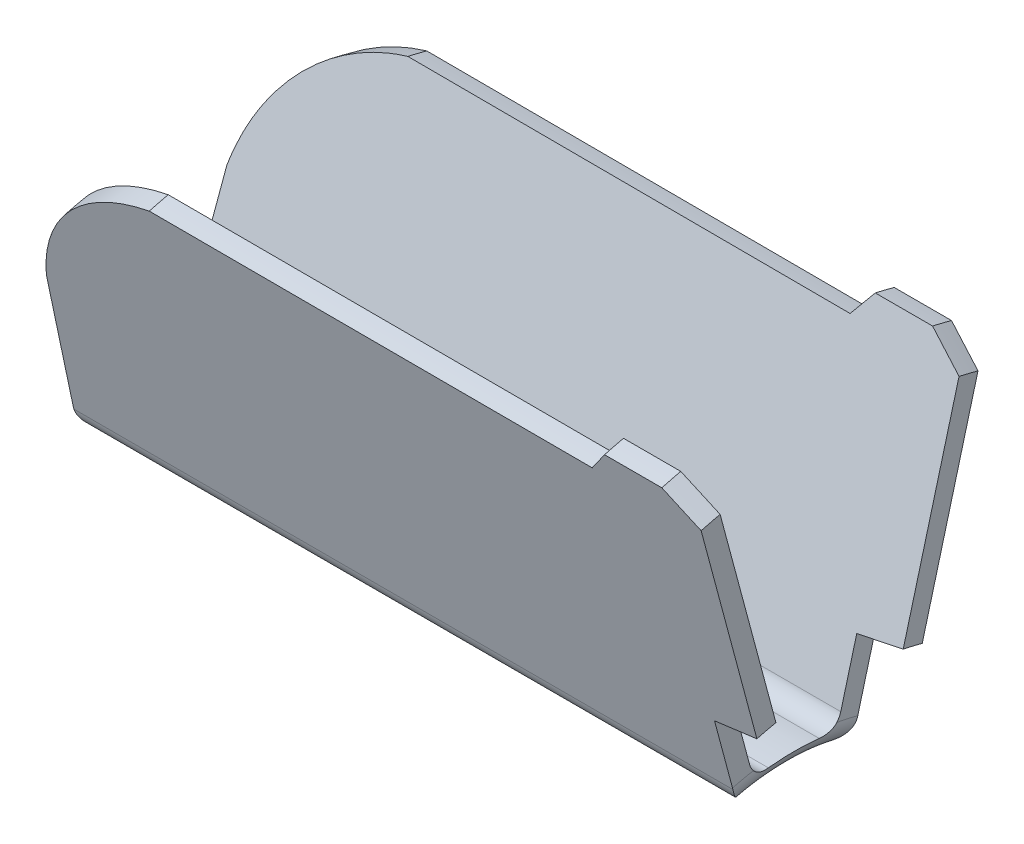
SolidWorks part; units mm, degrees
material "AISI 1045 Steel, cold drawn"
ref_plane "Front Plane" through (0, 0, 0) normal (0, 0, 1) x (1, 0, 0)
ref_plane "Top Plane" through (0, 0, 0) normal (0, 1, 0) x (1, 0, 0)
ref_plane "Right Plane" through (0, 0, 0) normal (1, 0, 0) x (0, 0, -1)
sketch "Sketch1" plane through (0, 0, 0) normal (0, 0, 1) x (1, 0, 0)
  line L0 (0, 0) -> (70.39, 0) construction
  line L1 (-21.1448, -22.76) -> (121.8609, -22.76) construction
  line L2 (70.39, 0) -> (75.12, 0) construction
  line L3 (70.39, 0) -> (70.39, 10.41)
  line L4 (70.39, 10.41) -> (75.12, 11.25)
  line L5 (75.12, 11.25) -> (75.12, 34.19)
  line L6 (75.12, 34.19) -> (71.6166, 36.83)
  line L7 (75.12, 34.19) -> (63.52, 34.19) construction
  line L8 (71.6166, 36.83) -> (65.5166, 36.83)
  line L9 (65.5166, 36.83) -> (63.52, 34.19)
  line L10 (16.39, 0) -> (16.39, 34.32) construction
  line L11 (63.52, 34.19) -> (16.39, 34.32)
  line L12 (0, 0) -> (1.2784, 18.282)
  line L13 (0, 0) -> (70.39, 0)
  arc A0 (1.2784, 18.282) -> (16.39, 34.32) centre (21.5455, 14.3239) cw
  dimension "D15" = 20.65
  dimension "D1" = 70.39
  dimension "D2" = 22.76
  dimension "D3" = 75.12
  dimension "D4" = 33.17
  dimension "D5" = 34.01
  dimension "D6" = 56.95
  dimension "D7" = 59.59
  dimension "D8" = 37
  dimension "D9" = 75.12
  dimension "D10" = 11.6
  dimension "D11" = 6.1
  dimension "D12" = 57.08
  dimension "D13" = 47.13
  dimension "D14" = 86
revolve "Revolve1" add sketch "Sketch1" angle 15 about L1
sketch "Sketch2" plane through (75.12, 0, 0) normal (1, 0, 0) x (0, 0, -1)
  line L0 (0, 0) -> (0, -22.86) construction
  line L1 (0, 0) -> (0, 48.3728) construction
  line L2 (-15.0305, 41.3709) -> (-4.857, 3.4031)
  line L3 (-8.8024, 10.0911) -> (-14.7397, 32.2495) construction
  line L4 (-15.0305, 41.3709) -> (15.0305, 41.3709)
  line L5 (15.0305, 41.3709) -> (4.857, 3.4031)
  arc A0 (-2.708, 1.9325) -> (-4.857, 3.4031) centre (-2.9252, 3.9207) cw
  arc A1 (2.708, 1.9325) -> (-2.708, 1.9325) centre (0, -22.86) ccw
  arc A2 (2.708, 1.9325) -> (4.857, 3.4031) centre (2.9252, 3.9207) ccw
  point P10 (0, 41.3709)
  point P13 (-4.3978, 1.6892)
  point P16 (4.3978, 1.6892)
  dimension "D2" = 2
  dimension "D4" = 2
  dimension "D1" = 22.86
  dimension "D3" = 2.08
extrude "Cut-Extrude1" cut sketch "Sketch2" against normal blind 100
fillet "Fillet2" radius 3 4 edges at (35.195, -0.7755, 5.8907) (70.39, 0, 0) (35.195, -0.7755, -5.8907) (0, 0, 0)
